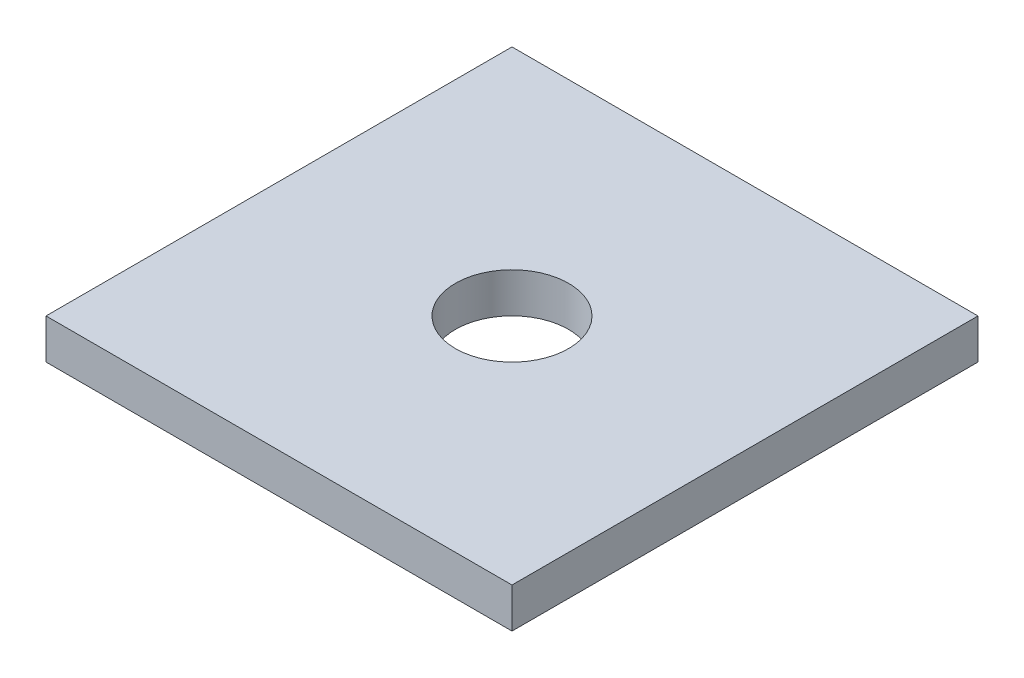
SolidWorks part; units mm, degrees
note: The reader was unsure of these and kept them because the rebuilt part matched: thickness of "Базовая кромка1", "Листовой металл3".
material "AISI 304"
ref_plane "Спереди" through (0, 0, 0) normal (0, 0, 1) x (1, 0, 0)
ref_plane "Сверху" through (0, 0, 0) normal (0, 1, 0) x (1, 0, 0)
ref_plane "Справа" through (0, 0, 0) normal (1, 0, 0) x (0, 0, -1)
sketch "Эскиз1" plane through (0, 0, 0) normal (0, 1, 0) x (1, 0, 0)
  line L1 (-35, 35) -> (35, 35)
  line L2 (-35, 35) -> (-35, -35)
  line L3 (-35, -35) -> (35, -35)
  line L4 (35, 35) -> (35, -35)
  line L5 (-35, 35) -> (35, -35) construction
  line L6 (-35, -35) -> (35, 35) construction
  line L7 (-1.5, 0) -> (1.5, 0) construction
  line L14 (-1.5, 8.5) -> (1.5, 8.5) construction
  line L15 (-1.5, -8.5) -> (1.5, -8.5) construction
  circle A3 centre (0, 0) radius 8.5
  arc A9 (-1.5, 8.5) -> (-1.5, -8.5) centre (-1.5, 0) ccw construction
  arc A10 (1.5, -8.5) -> (1.5, 8.5) centre (1.5, 0) ccw construction
  point P0 (0, 0)
  point P5 (0, 0)
  point P14 (0, 0)
  dimension "D5" = 17
  dimension "D1" = 70
  dimension "D2" = 70
  dimension "D6" = 3
base flange "Базовая кромка1" sketch "Эскиз1" thickness 6 reverse thickness direction no parameters "D1"=4
fillet "Скругление1" [suppressed] radius 20
sketch "Сгиб-Линии1" plane through (0, 0, 0) normal (0, 1, 0) x (1, 0, 0)
sketch "Граничная рамка1" plane through (0, 0, 0) normal (0, 1, 0) x (1, 0, 0)
sheet metal parameters "Листовой металл3" thickness 6 parameters "D1"=4
flat pattern "Развертка3" [suppressed]
sketch "Сгиб-Линии2" plane through (0, 0, 0) normal (0, 1, 0) x (1, 0, 0)
sketch "Граничная рамка2" [suppressed] plane through (0, 0, 0) normal (0, 1, 0) x (1, 0, 0)
